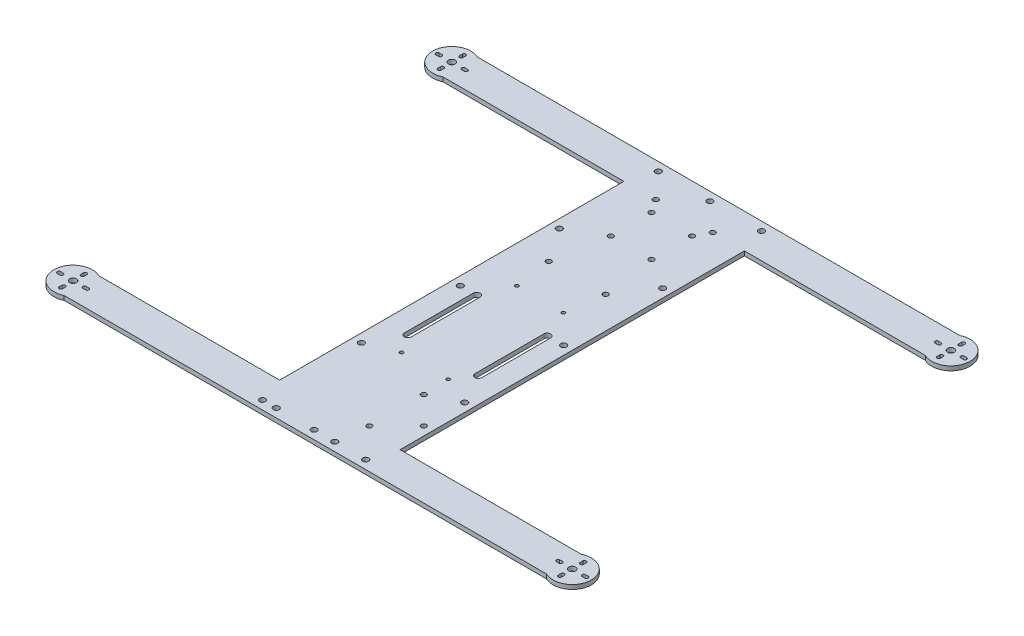
SolidWorks part; units mm, degrees
ref_plane "Front Plane" through (0, 0, 0) normal (0, 0, 1) x (1, 0, 0)
ref_plane "Top Plane" through (0, 0, 0) normal (0, 1, 0) x (1, 0, 0)
ref_plane "Right Plane" through (0, 0, 0) normal (1, 0, 0) x (0, 0, -1)
sketch "Sketch2" plane through (0, 0, 0) normal (0, 1, 0) x (1, 0, 0)
  line L0 (-44.45, 0) -> (44.45, 0) construction
  line L1 (-41.275, 152.4) -> (41.275, 152.4)
  line L2 (-44.45, 149.225) -> (-44.45, -149.225)
  line L3 (-41.275, -152.4) -> (41.275, -152.4)
  line L4 (44.45, 149.225) -> (44.45, -149.225)
  line L5 (0, 152.4) -> (0, -152.4) construction
  arc A0 (-44.45, -149.225) -> (-41.275, -152.4) centre (-41.275, -149.225) ccw
  arc A1 (41.275, -152.4) -> (44.45, -149.225) centre (41.275, -149.225) ccw
  arc A2 (41.275, 152.4) -> (44.45, 149.225) centre (41.275, 149.225) cw
  arc A3 (-41.275, 152.4) -> (-44.45, 149.225) centre (-41.275, 149.225) ccw
  point P8 (0, 0)
  point P13 (-44.45, -152.4)
  point P16 (44.45, -152.4)
  point P21 (-44.45, 152.4)
  dimension "D3" = 3.175
  dimension "D1" = 304.8
  dimension "D2" = 88.9
extrude "Plate Thickness" add sketch "Sketch2" along normal blind 3.175 contours L2 A0 L3 A1 L4 A2 L1 A3
sketch "Sketch10" plane through (0, 3.175, 0) normal (0, 1, 0) x (1, 0, 0)
  line L1 (41.275, 152.4) -> (177.986, 152.4)
  line L2 (41.275, 152.4) -> (41.275, 127)
  line L3 (41.275, 127) -> (177.986, 127)
  line L5 (44.45, 149.225) -> (44.45, -149.225) construction
  line L6 (0, 0) -> (0, 234.1968) construction
  line L7 (0, 0) -> (254.2756, 0) construction
  line L8 (41.275, -127) -> (177.986, -127)
  line L9 (41.275, -152.4) -> (41.275, -127)
  line L10 (41.275, -152.4) -> (177.986, -152.4)
  line L11 (41.275, 152.4) -> (177.986, 152.4)
  line L12 (41.275, 152.4) -> (41.275, 127)
  line L13 (41.275, 127) -> (177.986, 127)
  line L14 (41.275, -127) -> (177.986, -127)
  line L15 (41.275, -152.4) -> (41.275, -127)
  line L16 (41.275, -152.4) -> (177.986, -152.4)
  line L17 (41.275, 152.4) -> (177.986, 152.4)
  line L18 (41.275, 152.4) -> (41.275, 127)
  line L19 (41.275, 127) -> (177.986, 127)
  line L20 (41.275, -127) -> (177.986, -127)
  line L21 (41.275, -152.4) -> (41.275, -127)
  line L22 (41.275, -152.4) -> (177.986, -152.4)
  line L23 (41.275, 152.4) -> (177.986, 152.4)
  line L24 (41.275, 152.4) -> (41.275, 127)
  line L25 (41.275, 127) -> (177.986, 127)
  line L26 (41.275, -127) -> (177.986, -127)
  line L27 (41.275, -152.4) -> (41.275, -127)
  line L28 (41.275, -152.4) -> (177.986, -152.4)
  line L29 (-41.275, -127) -> (-177.986, -127)
  line L30 (-41.275, -152.4) -> (-41.275, -127)
  line L31 (-41.275, -152.4) -> (-177.986, -152.4)
  line L32 (-41.275, 127) -> (-177.986, 127)
  line L33 (-41.275, 152.4) -> (-41.275, 127)
  line L34 (-41.275, 152.4) -> (-177.986, 152.4)
  arc A0 (177.986, 127) -> (177.986, 152.4) centre (184.15, 139.7) ccw
  arc A1 (177.986, -127) -> (177.986, -152.4) centre (184.15, -139.7) cw
  arc A2 (177.986, 127) -> (177.986, 152.4) centre (184.15, 139.7) ccw
  arc A3 (177.986, -127) -> (177.986, -152.4) centre (184.15, -139.7) cw
  arc A4 (177.986, 127) -> (177.986, 152.4) centre (184.15, 139.7) ccw
  arc A5 (177.986, -127) -> (177.986, -152.4) centre (184.15, -139.7) cw
  arc A6 (177.986, 127) -> (177.986, 152.4) centre (184.15, 139.7) ccw
  arc A7 (177.986, -127) -> (177.986, -152.4) centre (184.15, -139.7) cw
  arc A8 (-177.986, -127) -> (-177.986, -152.4) centre (-184.15, -139.7) ccw
  arc A9 (-177.986, 127) -> (-177.986, 152.4) centre (-184.15, 139.7) cw
  arc M45 (-41.275, 152.4) -> (-44.45, 149.225) centre (-41.275, 149.225) ccw
  line M46 (-44.45, 149.225) -> (-44.45, -149.225)
  arc M47 (-44.45, -149.225) -> (-41.275, -152.4) centre (-41.275, -149.225) ccw
  arc M49 (41.275, -152.4) -> (44.45, -149.225) centre (41.275, -149.225) ccw
  line M50 (44.45, -149.225) -> (44.45, 149.225)
  arc M51 (44.45, 149.225) -> (41.275, 152.4) centre (41.275, 149.225) ccw
  dimension "D1" = 139.7
  dimension "D2" = 25.4
extrude "Boss-Extrude1" add sketch "Sketch10" against normal up to surface (3.175 mm away) contours A9 L32 L34 M46 M45 | L3 A0 L1 M51 M50 | A1 L8 L10 M50 M49 | L29 A8 L31 M47 M46 region at (120.5918, 3.175, 139.7067) region at (120.5918, 3.175, -139.7067) region at (-120.5918, 3.175, -139.7067) region at (-120.5918, 3.175, 139.7067) up to face at (0, 0, 0)
sketch "Sketch3" plane through (0, 3.175, 0) normal (0, 1, 0) x (1, 0, 0)
  line L0 (-44.45, 127) -> (-44.45, -127) construction
  line L1 (-177.986, 152.4) -> (177.986, 152.4) construction
  line L2 (-44.45, 0) -> (152.1758, 0) construction
  line L3 (-44.45, 127) -> (-44.45, -127) construction
  line L4 (0, 152.4) -> (0, -152.4) construction
  line L5 (-177.986, -152.4) -> (177.986, -152.4) construction
  circle A0 centre (-38.1, 146.05) radius 2.159
  circle A1 centre (-38.1, 73.025) radius 2.159
  circle A2 centre (-38.1, -73.025) radius 2.159
  circle A3 centre (-38.1, -146.05) radius 2.159
  circle A4 centre (38.1, -146.05) radius 2.159
  circle A5 centre (38.1, -73.025) radius 2.159
  circle A6 centre (38.1, 73.025) radius 2.159
  circle A7 centre (38.1, 146.05) radius 2.159
  circle A8 centre (0, 146.05) radius 2.159
  circle A9 centre (0, -146.05) radius 2.159
  circle A10 centre (-38.1, 0) radius 2.159
  circle A11 centre (38.1, 0) radius 2.159
  point P37 (0, 0)
  point P38 (0, 0)
  point P39 (0, 0)
  point P40 (0, 0)
  dimension "D1" = 4.318
  dimension "D4" = 4.318
  dimension "D2" = 6.35
  dimension "D3" = 6.35
  dimension "D5" = 73.025
  dimension "D6" = 6.35
  dimension "D7" = 73.025
  dimension "D8" = 73.025
  dimension "D9" = 73.025
extrude "Mounting holes" cut sketch "Sketch3" against normal through all
sketch "Sketch4" plane through (0, 3.175, 0) normal (0, 1, 0) x (1, 0, 0)
  line L0 (-21.0058, 48.0812) -> (21.0058, 48.0812) construction
  line L1 (0, 0) -> (0, 139.7) construction
  circle A0 centre (-21.0058, 127.0752) radius 1.905
  circle A1 centre (-21.0058, 48.0812) radius 1.905
  circle A2 centre (21.0058, 48.0812) radius 1.905
  circle A3 centre (21.0058, 127.0752) radius 1.905
  point P13 (0, 48.0812)
  point P17 (0, 69.85)
  point P18 (0, 69.85)
  dimension "D1" = 3.81
  dimension "D2" = 78.994
  dimension "D3" = 42.0116
extrude "Jetson Holes (w/o mount)" cut sketch "Sketch4" against normal through all
sketch "Sketch5" plane through (0, 3.175, 0) normal (0, 1, 0) x (1, 0, 0)
  circle A1 centre (-14.3419, 117.2351) radius 1.905
  circle A3 centre (15.6555, 117.2351) radius 1.905
  circle A4 centre (15.6555, 87.2377) radius 1.905
  circle A5 centre (-14.3419, 87.2377) radius 1.905
  dimension "D1" = 3.81
  dimension "D2" = 29.9974
  dimension "D3" = 29.9974
extrude "PDB holes" cut sketch "Sketch5" against normal through all
sketch "Sketch6" plane through (0, 3.175, 0) normal (0, 1, 0) x (1, 0, 0)
  circle A6 centre (38.0032, -103.0828) radius 1.905
  circle A7 centre (17.9372, -83.0168) radius 1.905
  circle A8 centre (17.9372, -123.1488) radius 1.905
  dimension "D5" = 3.81
  dimension "D6" = 40.132
  dimension "D7" = 20.066
  dimension "D8" = 20.066
extrude "Lidar Holes" cut sketch "Sketch6" against normal through all
sketch "Sketch7" plane through (0, 3.175, 0) normal (0, 1, 0) x (1, 0, 0)
  line L0 (0, 152.4) -> (0, -152.4) construction
  line L1 (-177.986, 152.4) -> (177.986, 152.4) construction
  line L2 (-177.986, -152.4) -> (177.986, -152.4) construction
  line L3 (17.145, 20.7699) -> (-17.145, 20.7699) construction
  circle A0 centre (-17.145, 20.7699) radius 1.27
  circle A1 centre (-17.145, -64.3201) radius 1.27
  circle A2 centre (17.145, -64.3201) radius 1.27
  circle A3 centre (17.145, 20.7699) radius 1.27
  point P14 (0, 20.7699)
  dimension "D1" = 2.54
  dimension "D2" = 85.09
  dimension "D3" = 34.29
extrude "PixHawk Holes" cut sketch "Sketch7" against normal through all
sketch "Sketch8" plane through (0, 3.175, 0) normal (0, 1, 0) x (1, 0, 0)
  line L0 (0, 152.4) -> (0, -115.5095) construction
  line L1 (-177.986, 152.4) -> (177.986, 152.4) construction
  line L2 (-26.035, -0.006) -> (-26.035, -50.806) construction
  line L3 (-23.495, -0.006) -> (-23.495, -50.806)
  line L4 (-28.575, -0.006) -> (-28.575, -50.806)
  line L5 (26.035, -0.006) -> (26.035, -50.806) construction
  line L6 (23.495, -0.006) -> (23.495, -50.806)
  line L7 (28.575, -0.006) -> (28.575, -50.806)
  arc A0 (-23.495, -0.006) -> (-28.575, -0.006) centre (-26.035, -0.006) ccw
  arc A1 (-28.575, -50.806) -> (-23.495, -50.806) centre (-26.035, -50.806) ccw
  arc A2 (23.495, -0.006) -> (28.575, -0.006) centre (26.035, -0.006) cw
  arc A3 (28.575, -50.806) -> (23.495, -50.806) centre (26.035, -50.806) cw
  point P7 (-26.035, -25.406)
  point P14 (26.035, -25.406)
  dimension "D1" = 50.8
  dimension "D2" = 5.08
  dimension "D3" = 26.035
extrude "Battery Holes" cut sketch "Sketch8" against normal through all
sketch "Sketch9" plane through (0, 3.175, 0) normal (0, 1, 0) x (1, 0, 0)
  line L0 (-177.986, -152.4) -> (177.986, -152.4) construction
  circle A0 centre (-27.8687, -146.05) radius 2.159
  circle A1 centre (15.3113, -146.05) radius 2.159
  dimension "D1" = 4.318
  dimension "D2" = 4.318
  dimension "D3" = 43.18
  dimension "D4" = 6.35
extrude "Stereo Cam" cut sketch "Sketch9" against normal through all
sketch "Sketch11" plane through (0, 3.175, 0) normal (0, 1, 0) x (1, 0, 0)
  line L0 (173.65, 139.7) -> (175.65, 139.7) construction
  line L1 (173.65, 140.95) -> (175.65, 140.95)
  line L2 (173.65, 138.45) -> (175.65, 138.45)
  line L3 (184.15, 139.7) -> (184.15, 143.0164) construction
  line L4 (194.65, 139.7) -> (192.65, 139.7) construction
  line L5 (194.65, 140.95) -> (192.65, 140.95)
  line L6 (194.65, 138.45) -> (192.65, 138.45)
  line L7 (184.15, 148.7) -> (184.15, 146.7) construction
  line L8 (185.4, 148.7) -> (185.4, 146.7)
  line L9 (182.9, 148.7) -> (182.9, 146.7)
  line L10 (184.15, 139.7) -> (199.8184, 139.7) construction
  line L11 (184.15, 130.7) -> (184.15, 132.7) construction
  line L12 (185.4, 130.7) -> (185.4, 132.7)
  line L13 (182.9, 130.7) -> (182.9, 132.7)
  line L14 (44.45, 127) -> (44.45, -127) construction
  line L15 (-177.986, 152.4) -> (177.986, 152.4) construction
  line L16 (0, 0) -> (0, 273.2731) construction
  line L19 (0, 0) -> (202.4297, 0) construction
  line L22 (184.15, -139.7) -> (199.8184, -139.7) construction
  line L25 (184.15, -139.7) -> (184.15, -143.0164) construction
  line L28 (184.15, -130.7) -> (184.15, -132.7) construction
  line L29 (185.4, -130.7) -> (185.4, -132.7)
  line L30 (182.9, -130.7) -> (182.9, -132.7)
  line L33 (184.15, -148.7) -> (184.15, -146.7) construction
  line L36 (185.4, -148.7) -> (185.4, -146.7)
  line L39 (182.9, -148.7) -> (182.9, -146.7)
  line L42 (194.65, -139.7) -> (192.65, -139.7) construction
  line L43 (194.65, -140.95) -> (192.65, -140.95)
  line L44 (194.65, -138.45) -> (192.65, -138.45)
  line L45 (173.65, -139.7) -> (175.65, -139.7) construction
  line L46 (173.65, -140.95) -> (175.65, -140.95)
  line L49 (173.65, -138.45) -> (175.65, -138.45)
  line L52 (-184.15, -139.7) -> (-184.15, -143.0164) construction
  line L55 (-184.15, -139.7) -> (-199.8184, -139.7) construction
  line L58 (-173.65, -139.7) -> (-175.65, -139.7) construction
  line L59 (-173.65, -140.95) -> (-175.65, -140.95)
  line L60 (-173.65, -138.45) -> (-175.65, -138.45)
  line L61 (-184.15, -148.7) -> (-184.15, -146.7) construction
  line L62 (-185.4, -148.7) -> (-185.4, -146.7)
  line L63 (-182.9, -148.7) -> (-182.9, -146.7)
  line L64 (-184.15, -130.7) -> (-184.15, -132.7) construction
  line L65 (-185.4, -130.7) -> (-185.4, -132.7)
  line L66 (-182.9, -130.7) -> (-182.9, -132.7)
  line L67 (-194.65, -139.7) -> (-192.65, -139.7) construction
  line L68 (-194.65, -140.95) -> (-192.65, -140.95)
  line L69 (-194.65, -138.45) -> (-192.65, -138.45)
  line L70 (-184.15, 139.7) -> (-199.8184, 139.7) construction
  line L71 (-184.15, 139.7) -> (-184.15, 143.0164) construction
  line L72 (-184.15, 130.7) -> (-184.15, 132.7) construction
  line L73 (-185.4, 130.7) -> (-185.4, 132.7)
  line L74 (-182.9, 130.7) -> (-182.9, 132.7)
  line L75 (-184.15, 148.7) -> (-184.15, 146.7) construction
  line L76 (-185.4, 148.7) -> (-185.4, 146.7)
  line L77 (-182.9, 148.7) -> (-182.9, 146.7)
  line L78 (-194.65, 139.7) -> (-192.65, 139.7) construction
  line L79 (-194.65, 140.95) -> (-192.65, 140.95)
  line L80 (-194.65, 138.45) -> (-192.65, 138.45)
  line L81 (-173.65, 139.7) -> (-175.65, 139.7) construction
  line L82 (-173.65, 140.95) -> (-175.65, 140.95)
  line L83 (-173.65, 138.45) -> (-175.65, 138.45)
  circle A0 centre (184.15, 139.7) radius 2.5
  arc A1 (173.65, 140.95) -> (173.65, 138.45) centre (173.65, 139.7) ccw
  arc A2 (175.65, 138.45) -> (175.65, 140.95) centre (175.65, 139.7) ccw
  arc A4 (194.65, 140.95) -> (194.65, 138.45) centre (194.65, 139.7) cw
  arc A5 (192.65, 138.45) -> (192.65, 140.95) centre (192.65, 139.7) cw
  arc A6 (185.4, 148.7) -> (182.9, 148.7) centre (184.15, 148.7) ccw
  arc A7 (182.9, 146.7) -> (185.4, 146.7) centre (184.15, 146.7) ccw
  arc A8 (185.4, 130.7) -> (182.9, 130.7) centre (184.15, 130.7) cw
  arc A9 (182.9, 132.7) -> (185.4, 132.7) centre (184.15, 132.7) cw
  circle A37 centre (184.15, -139.7) radius 2.5
  arc A38 (185.4, -130.7) -> (182.9, -130.7) centre (184.15, -130.7) ccw
  arc A39 (182.9, -132.7) -> (185.4, -132.7) centre (184.15, -132.7) ccw
  arc A40 (185.4, -148.7) -> (182.9, -148.7) centre (184.15, -148.7) cw
  arc A41 (182.9, -146.7) -> (185.4, -146.7) centre (184.15, -146.7) cw
  arc A42 (194.65, -140.95) -> (194.65, -138.45) centre (194.65, -139.7) ccw
  arc A43 (192.65, -138.45) -> (192.65, -140.95) centre (192.65, -139.7) ccw
  arc A44 (173.65, -140.95) -> (173.65, -138.45) centre (173.65, -139.7) cw
  arc A45 (175.65, -138.45) -> (175.65, -140.95) centre (175.65, -139.7) cw
  circle A46 centre (-184.15, -139.7) radius 2.5
  arc A47 (-173.65, -140.95) -> (-173.65, -138.45) centre (-173.65, -139.7) ccw
  arc A48 (-175.65, -138.45) -> (-175.65, -140.95) centre (-175.65, -139.7) ccw
  arc A49 (-185.4, -148.7) -> (-182.9, -148.7) centre (-184.15, -148.7) ccw
  arc A50 (-182.9, -146.7) -> (-185.4, -146.7) centre (-184.15, -146.7) ccw
  arc A51 (-185.4, -130.7) -> (-182.9, -130.7) centre (-184.15, -130.7) cw
  arc A52 (-182.9, -132.7) -> (-185.4, -132.7) centre (-184.15, -132.7) cw
  arc A53 (-194.65, -140.95) -> (-194.65, -138.45) centre (-194.65, -139.7) cw
  arc A54 (-192.65, -138.45) -> (-192.65, -140.95) centre (-192.65, -139.7) cw
  circle A55 centre (-184.15, 139.7) radius 2.5
  arc A56 (-185.4, 130.7) -> (-182.9, 130.7) centre (-184.15, 130.7) ccw
  arc A57 (-182.9, 132.7) -> (-185.4, 132.7) centre (-184.15, 132.7) ccw
  arc A58 (-185.4, 148.7) -> (-182.9, 148.7) centre (-184.15, 148.7) cw
  arc A59 (-182.9, 146.7) -> (-185.4, 146.7) centre (-184.15, 146.7) cw
  arc A60 (-194.65, 140.95) -> (-194.65, 138.45) centre (-194.65, 139.7) ccw
  arc A61 (-192.65, 138.45) -> (-192.65, 140.95) centre (-192.65, 139.7) ccw
  arc A62 (-173.65, 140.95) -> (-173.65, 138.45) centre (-173.65, 139.7) cw
  arc A63 (-175.65, 138.45) -> (-175.65, 140.95) centre (-175.65, 139.7) cw
  point P5 (174.65, 139.7)
  point P16 (193.65, 139.7)
  point P23 (184.15, 147.7)
  point P31 (184.15, 131.7)
  point P47 (184.15, -131.7)
  point P54 (184.15, -147.7)
  point P61 (193.65, -139.7)
  point P68 (174.65, -139.7)
  point P79 (-174.65, -139.7)
  point P86 (-184.15, -147.7)
  point P93 (-184.15, -131.7)
  point P100 (-193.65, -139.7)
  point P111 (-184.15, 131.7)
  point P118 (-184.15, 147.7)
  point P125 (-193.65, 139.7)
  point P132 (-174.65, 139.7)
  dimension "D1" = 5
  dimension "D2" = 2.5
  dimension "D3" = 2
  dimension "D4" = 19
  dimension "D5" = 2.5
  dimension "D6" = 2
  dimension "D7" = 16
  dimension "D8" = 139.7
  dimension "D9" = 12.7
extrude "motor mounting" cut sketch "Sketch11" against normal through all
